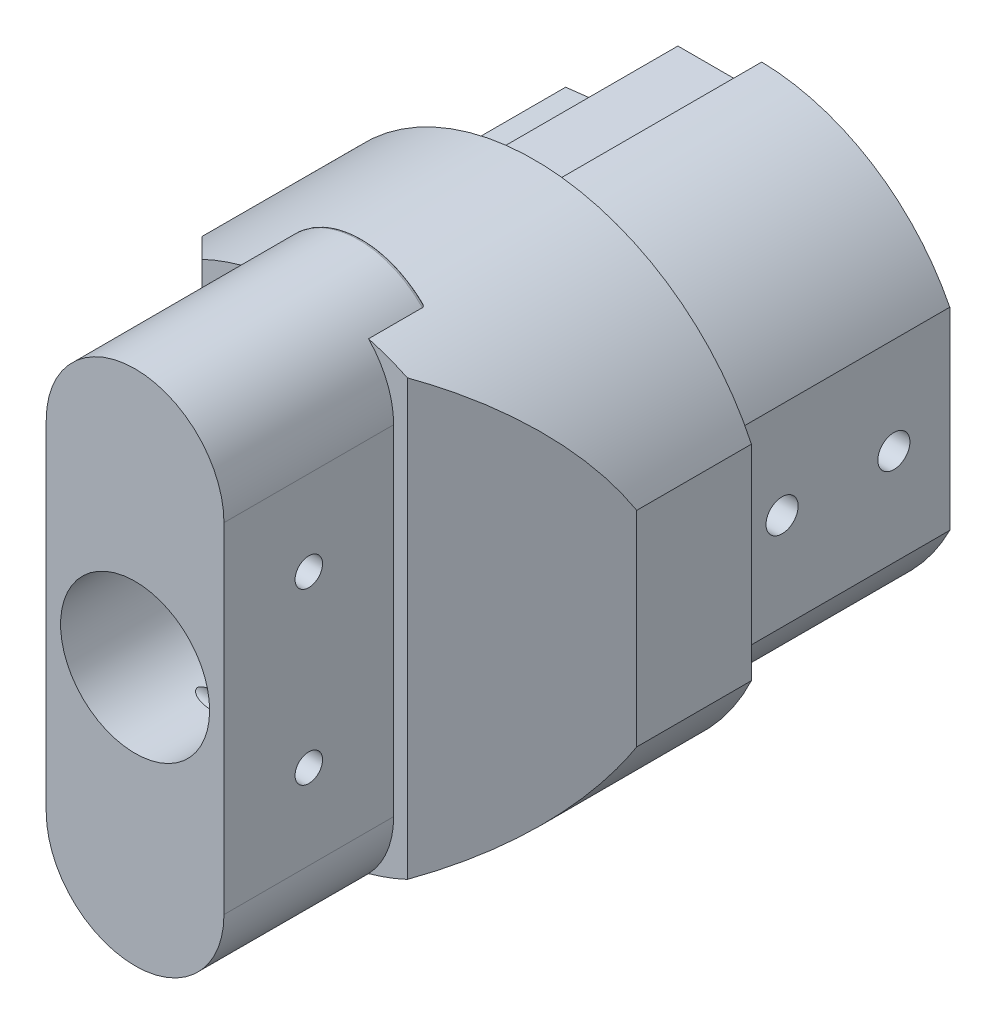
SolidWorks part; units mm, degrees
ref_plane "Front Plane" through (0, 0, 0) normal (0, 0, 1) x (1, 0, 0)
ref_plane "Top Plane" through (0, 0, 0) normal (0, 1, 0) x (1, 0, 0)
ref_plane "Right Plane" through (0, 0, 0) normal (1, 0, 0) x (0, 0, -1)
sketch "Sketch1" plane through (0, 0, 0) normal (0, 0, 1) x (1, 0, 0)
  line L87 (-18.4999, -8.3443) -> (-14.211, -8.8372)
  line L88 (-8.712, -10.4234) -> (-8.712, -16.3483)
  line L89 (-8.712, -16.3483) -> (0.2, -16.3483)
  line L90 (0.2, -16.3483) -> (0.2, -18.6974)
  line L91 (15, -8.4753) -> (15, 8.377)
  line L92 (-1.4, 18.6976) -> (-1.4, 16.25)
  line L93 (-1.4, 16.25) -> (-8.712, 16.25)
  line L94 (-8.712, 16.25) -> (-8.712, 10.3251)
  line L95 (-14.211, 8.7389) -> (-18.4999, 8.246)
  line L96 (-18.4999, 8.246) -> (-18.4999, -8.3443)
  line L97 (-18.4999, -8.3443) -> (-14.211, -8.8372)
  line L98 (-8.712, -10.4234) -> (-8.712, -16.3483)
  line L99 (-8.712, -16.3483) -> (0.2, -16.3483)
  line L100 (0.2, -16.3483) -> (0.2, -18.6974)
  line L101 (15, -8.4753) -> (15, 8.377)
  line L102 (-1.4, 18.6976) -> (-1.4, 16.25)
  line L103 (-1.4, 16.25) -> (-8.712, 16.25)
  line L104 (-8.712, 16.25) -> (-8.712, 10.3251)
  line L105 (-14.211, 8.7389) -> (-18.4999, 8.246)
  line L106 (-18.4999, 8.246) -> (-18.4999, -8.3443)
  arc A32 (-14.211, -8.8372) -> (-8.712, -10.4234) centre (-8.712, -0.0983) ccw
  arc A33 (0.2, -18.6974) -> (15, -8.4753) centre (-1.75, -0.0491) ccw
  arc A34 (15, 8.377) -> (-1.4, 18.6976) centre (-1.75, -0.0491) ccw
  arc A35 (-8.712, 10.3251) -> (-14.211, 8.7389) centre (-8.712, 0) ccw
  arc A36 (-14.211, -8.8372) -> (-8.712, -10.4234) centre (-8.712, -0.0983) ccw
  arc A37 (0.2, -18.6974) -> (15, -8.4753) centre (-1.75, -0.0491) ccw
  arc A38 (15, 8.377) -> (-1.4, 18.6976) centre (-1.75, -0.0491) ccw
  arc A39 (-8.712, 10.3251) -> (-14.211, 8.7389) centre (-8.712, 0) ccw
  dimension "D1" = 0.2
extrude "Boss-Extrude1" add sketch "Sketch1" against normal blind 19.5
sketch "Sketch3" plane through (0, 0, 0) normal (0, 0, 1) x (1, 0, 0)
  line L21 (-20.6999, 8.8839) -> (-20.6999, -8.9822)
  line L22 (17.2, -8.9822) -> (17.2, 8.8839)
  line L23 (-20.6999, 8.8839) -> (-20.6999, -8.9822)
  line L24 (17.2, -8.9822) -> (17.2, 8.8839)
  arc A17 (17.2, 8.8839) -> (-20.6999, 8.8839) centre (-1.75, -0.0491) ccw
  arc A18 (-20.6999, -8.9822) -> (17.2, -8.9822) centre (-1.75, -0.0491) ccw
  arc A19 (17.2, 8.8839) -> (-20.6999, 8.8839) centre (-1.75, -0.0491) ccw
  arc A20 (-20.6999, -8.9822) -> (17.2, -8.9822) centre (-1.75, -0.0491) ccw
  dimension "D2" = 0
sketch "Sketch4" plane through (0, 0, 0) normal (0, 0, 1) x (1, 0, 0)
  line L6 (17.2, -8.9822) -> (17.2, 8.8839)
  line L7 (-20.6999, 8.8839) -> (-20.6999, -8.9822)
  line L8 (17.2, -8.9822) -> (17.2, 8.8839)
  line L9 (-20.6999, 8.8839) -> (-20.6999, -8.9822)
  arc A8 (-20.6999, -8.9822) -> (17.2, -8.9822) centre (-1.75, -0.0491) ccw
  arc A9 (17.2, 8.8839) -> (-20.6999, 8.8839) centre (-1.75, -0.0491) ccw
  arc A10 (-20.6999, -8.9822) -> (17.2, -8.9822) centre (-1.75, -0.0491) ccw
  arc A11 (17.2, 8.8839) -> (-20.6999, 8.8839) centre (-1.75, -0.0491) ccw
  dimension "D1" = 0
extrude "Boss-Extrude4" add sketch "Sketch4" along normal blind 15
sketch "Sketch5" plane through (0, 0, 15) normal (0, 0, 1) x (1, 0, 0)
  line L0 (-9.5, 14.7509) -> (-9.5, -14.8491)
  line L1 (6, -14.8491) -> (6, 14.7509)
  arc A0 (-9.5, -14.8491) -> (6, -14.8491) centre (-1.75, -14.8491) ccw
  arc A1 (-9.5, 14.7509) -> (6, 14.7509) centre (-1.75, 14.7509) cw
extrude "Boss-Extrude5" add sketch "Sketch5" along normal blind 19.8
chamfer "Chamfer1" distance 11 angle 50 2 edges at (17.2, -0.0491, 15) (-20.6999, -0.0491, 15) first distance on face at (17.2, -0.0491, 7.5) first distance on face at (-20.6999, -0.0491, 7.5)
fillet "Fillet2" radius 0.3 2 edges at (-1.75, -22.5991, 15) (-1.75, 22.5009, 15)
sketch "Sketch6" plane through (0, 0, 34.8) normal (0, 0, 1) x (1, 0, 0)
  line L0 (-9.5, 14.7509) -> (6, -14.8491)
  line L1 (-9.5, -14.8491) -> (6, 14.7509)
  circle A0 centre (-1.75, -0.0491) radius 6.5
extrude "Cut-Extrude1" cut sketch "Sketch6" against normal through all contours L1 A0 L0 | L0 A0 L1 | L1 A0 L0 | L0 A0 L1 region at (-1.75, 4.1181, 34.8) region at (-5.277, -0.0491, 34.8) region at (1.7771, -0.0491, 34.8) region at (-1.75, -4.2163, 34.8)
extrude "Boss-Extrude3" add sketch "Sketch3" along normal blind 20
chamfer "Chamfer2" distance 10 angle 45 2 edges at (17.2, -0.0491, 20) (-20.6999, -0.0491, 20)
sketch "Sketch7" plane through (6, 0, 0) normal (1, 0, 0) x (0, 0, -1)
  circle A0 centre (-27.4, -7.4491) radius 1.2
  circle A1 centre (-27.4, 7.3509) radius 1.2
  point P1 (0, 0)
extrude "Cut-Extrude2" cut sketch "Sketch7" against normal through all
sketch "Sketch8" plane through (0, 0, 20) normal (0, 0, 1) x (1, 0, 0)
  circle A2 centre (-1.75, -0.0491) radius 6.5
  circle A3 centre (-1.75, -0.0491) radius 6.5
  dimension "D1" = 0
extrude "Cut-Extrude3" cut sketch "Sketch8" against normal through all
sketch "Sketch9" plane through (-18.4999, 0, 0) normal (-1, 0, 0) x (0, 0, 1)
  line L0 (-9.75, 8.246) -> (-9.75, -8.3443)
  line L1 (-19.5, 8.246) -> (0, 8.246) construction
  line L2 (-19.5, -8.3443) -> (0, -8.3443) construction
  circle A0 centre (-14.625, -0.0491) radius 1.4
  circle A1 centre (-4.875, -0.0246) radius 1.4
extrude "Cut-Extrude4" cut sketch "Sketch9" against normal through all contours A1 | A0 region at (-18.4999, -0.0491, -14.625) region at (-18.4999, -0.0246, -4.875)
sketch "Sketch10" plane through (-9.5, 0, 0) normal (-1, 0, 0) x (0, 0, 1)
  line L0 (27.4, 7.3509) -> (34.8, 7.3509)
  line L1 (34.8, 14.7509) -> (34.8, -14.8491) construction
  line L2 (34.8, 7.3509) -> (34.8, -0.0491)
  line L3 (0, 0) -> (-4.875, -0.0246)
  line L5 (-14.625, -0.0491) -> (-4.875, -0.0246)
